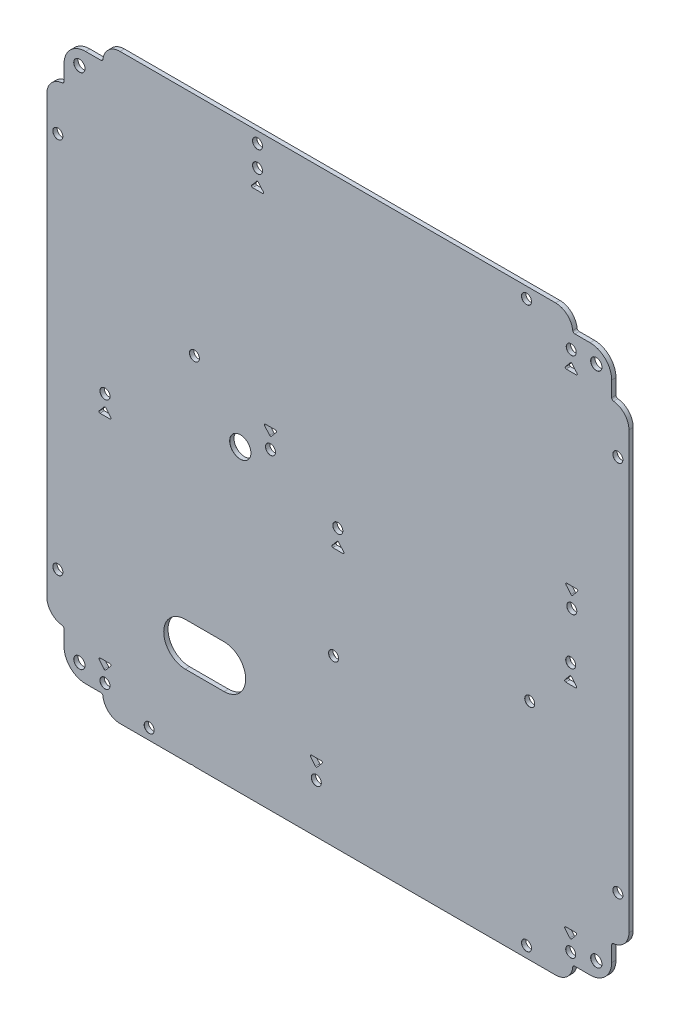
SolidWorks part; units mm, degrees
ref_plane "Front Plane" through (0, 0, 0) normal (0, 0, 1) x (1, 0, 0)
ref_plane "Top Plane" through (0, 0, 0) normal (0, 1, 0) x (1, 0, 0)
ref_plane "Right Plane" through (0, 0, 0) normal (1, 0, 0) x (0, 0, -1)
sketch "Sketch1" plane through (0, 0, 0) normal (0, 0, 1) x (1, 0, 0)
  line L1 (-135, -135) -> (135, -135)
  line L2 (-135, -135) -> (-135, 135)
  line L3 (-135, 135) -> (135, 135)
  line L4 (135, -135) -> (135, 135)
  line L5 (-135, -135) -> (135, 135) construction
  line L6 (-135, 135) -> (135, -135) construction
  point P0 (0, 0)
  dimension "D1" = 270
extrude "Boss-Extrude1" add sketch "Sketch1" along normal mid plane 2
sketch "Sketch5" plane through (0, 0, 0) normal (0, 0, 1) x (1, 0, 0)
  line L1 (-119.875, -119.875) -> (119.875, -119.875) construction
  line L2 (-119.875, -119.875) -> (-119.875, 119.875) construction
  line L3 (-119.875, 119.875) -> (119.875, 119.875) construction
  line L4 (119.875, -119.875) -> (119.875, 119.875) construction
  line L5 (-119.875, -119.875) -> (119.875, 119.875) construction
  line L6 (-119.875, 119.875) -> (119.875, -119.875) construction
  point P0 (0, 0)
  dimension "D1" = 239.75
hole_wizard "Ø5.2 (5.2) Diameter Hole1" positions "Sketch9" profile "Sketch11" hole size "Ø5.2" standard "ANSI Metric" end condition through all
sketch "Sketch9" plane through (0, 0, 1) normal (0, 0, 1) x (1, 0, 0)
  point P0 (119.875, 119.875)
  point P3 (119.875, -119.875)
  point P6 (-119.875, -119.875)
  point P9 (-119.875, 119.875)
sketch "Sketch11" plane through (119.875, 119.875, 1) normal (1, 0, 0) x (0, -1, 0)
  line L0 (0, 0) -> (0, 2)
  line L1 (0, 2) -> (2.625, 2)
  line L2 (2.6, 1.975) -> (2.6, 0.025)
  line L3 (2.6, 0.025) -> (2.625, 0)
  line L5 (2.625, 0) -> (0, 0)
  line L6 (-2.6, 0.025) -> (-2.625, 0) construction
  line L7 (2.625, 2) -> (2.6, 1.975)
  line L8 (-2.625, 2) -> (-2.6, 1.975) construction
  line L11 (0, -6.35) -> (0, 107.95) construction
  dimension "Thru Hole Dia." = 5.2
  dimension "Thru Hole Depth" = 2
  dimension "Near C'Sink Dia." = 5.25
  dimension "Near C'Sink Angle" = 90
  dimension "Far C'Sink Dia." = 5.25
  dimension "Far C'Sink Angle" = 90
sketch "Sketch12" plane through (0, 0, 0) normal (0, 0, 1) x (1, 0, 0)
  line L0 (-127, 109.9443) -> (-127, 117)
  line L1 (-117, 127) -> (-109.9443, 127)
  line L4 (-135, 101) -> (-135, 135)
  line L6 (-135, 135) -> (-101, 135)
  arc A0 (-127, 117) -> (-117, 127) centre (-117, 117) cw
  arc A1 (-108.9505, 127.8889) -> (-101, 135) centre (-101, 127) cw
  arc A2 (-127.8889, 108.9505) -> (-135, 101) centre (-127, 101) ccw
  arc A3 (-109.9443, 127) -> (-108.9505, 127.8889) centre (-109.9443, 128) ccw
  arc A4 (-127, 109.9443) -> (-127.8889, 108.9505) centre (-128, 109.9443) cw
  dimension "D1" = 10
  dimension "D2" = 8
  dimension "D5" = 1
  dimension "D3" = 34
  dimension "D4" = 8
extrude "Cut-Extrude1" cut sketch "Sketch12" against normal through all both and the other way through all
mirror "Mirror1" about plane through (0, 0, 0) normal (1, 0, 0) of "Cut-Extrude1" second plane through (0, 0, 0) second plane normal (0, 1, 0)
sketch "Sketch13" plane through (0, 0, 0) normal (0, 0, 1) x (1, 0, 0)
  line L1 (-129.875, -87.5) -> (129.875, -87.5) construction
  line L2 (-129.875, -87.5) -> (-129.875, 87.5) construction
  line L3 (-129.875, 87.5) -> (129.875, 87.5) construction
  line L4 (129.875, -87.5) -> (129.875, 87.5) construction
  line L5 (-129.875, -87.5) -> (129.875, 87.5) construction
  line L6 (-129.875, 87.5) -> (129.875, -87.5) construction
  point P0 (0, 0)
  dimension "D1" = 259.75
  dimension "D2" = 175
sketch "Sketch16" plane through (0, 0, 0) normal (0, 0, 1) x (1, 0, 0)
  line L0 (-135, 101) -> (-135, -101) construction
  line L1 (-87.5, -129.875) -> (87.5, -129.875) construction
  line L2 (-87.5, -129.875) -> (-87.5, 129.875) construction
  line L3 (-87.5, 129.875) -> (87.5, 129.875) construction
  line L4 (87.5, -129.875) -> (87.5, 129.875) construction
  line L5 (-87.5, -129.875) -> (87.5, 129.875) construction
  line L6 (-87.5, 129.875) -> (87.5, -129.875) construction
  point P0 (0, 0)
  point P6 (-37.25, 129.875)
  dimension "D1" = 175
  dimension "D2" = 259.75
  dimension "D3" = 97.75
hole_wizard "Ø4.6 (4.6) Diameter Hole1" positions "Sketch14" profile "Sketch15" hole size "Ø4.6" standard "ANSI Metric" end condition through all
sketch "Sketch14" plane through (0, 0, 1) normal (0, 0, 1) x (1, 0, 0)
  point P0 (129.875, 87.5)
  point P3 (129.875, -87.5)
  point P6 (-129.875, -87.5)
  point P9 (-129.875, 87.5)
  point P14 (-87.5, -129.875)
  point P17 (87.5, -129.875)
  point P20 (87.5, 129.875)
  point P24 (-37.25, 129.875)
sketch "Sketch15" plane through (129.875, 87.5, 1) normal (1, 0, 0) x (0, -1, 0)
  line L0 (0, 0) -> (0, 2)
  line L1 (0, 2) -> (2.325, 2)
  line L2 (2.3, 1.975) -> (2.3, 0.025)
  line L3 (2.3, 0.025) -> (2.325, 0)
  line L5 (2.325, 0) -> (0, 0)
  line L6 (-2.3, 0.025) -> (-2.325, 0) construction
  line L7 (2.325, 2) -> (2.3, 1.975)
  line L8 (-2.325, 2) -> (-2.3, 1.975) construction
  line L11 (0, -6.35) -> (0, 107.95) construction
  dimension "Thru Hole Dia." = 4.6
  dimension "Thru Hole Depth" = 2
  dimension "Near C'Sink Dia." = 4.65
  dimension "Near C'Sink Angle" = 90
  dimension "Far C'Sink Dia." = 4.65
  dimension "Far C'Sink Angle" = 90
sketch "Sketch17" plane through (0, 0, 0) normal (0, 0, 1) x (1, 0, 0)
  line L0 (-70.75, -88) -> (-52.75, -88) construction
  line L1 (-70.75, -78) -> (-52.75, -78)
  line L2 (-70.75, -98) -> (-52.75, -98)
  line L3 (-101, -135) -> (101, -135) construction
  line L4 (-135, 101) -> (-135, -101) construction
  arc A0 (-70.75, -78) -> (-70.75, -98) centre (-70.75, -88) ccw
  arc A1 (-52.75, -98) -> (-52.75, -78) centre (-52.75, -88) ccw
  point P2 (-61.75, -88)
  dimension "D2" = 38
  dimension "D1" = 20
  dimension "D3" = 37
  dimension "D4" = 54.25
extrude "Cut-Extrude2" cut sketch "Sketch17" along normal through all both and the other way through all
hole_wizard "Ø9.8 (9.8) Diameter Hole1" positions "Sketch18" profile "Sketch19" hole size "Ø9.8" standard "ANSI Metric" end condition through all
sketch "Sketch18" plane through (0, 0, 1) normal (0, 0, 1) x (1, 0, 0)
  line L0 (-135, 101) -> (-135, -101) construction
  line L1 (101, 135) -> (-101, 135) construction
  point P0 (-45.25, 4)
  dimension "D1" = 89.75
  dimension "D2" = 131
sketch "Sketch19" plane through (-45.25, 4, 1) normal (1, 0, 0) x (0, -1, 0)
  line L0 (0, 0) -> (0, 2)
  line L1 (0, 2) -> (4.925, 2)
  line L2 (4.9, 1.975) -> (4.9, 0.025)
  line L3 (4.9, 0.025) -> (4.925, 0)
  line L5 (4.925, 0) -> (0, 0)
  line L6 (-4.9, 0.025) -> (-4.925, 0) construction
  line L7 (4.925, 2) -> (4.9, 1.975)
  line L8 (-4.925, 2) -> (-4.9, 1.975) construction
  line L11 (0, -6.35) -> (0, 107.95) construction
  dimension "Thru Hole Dia." = 9.8
  dimension "Thru Hole Depth" = 2
  dimension "Near C'Sink Dia." = 9.85
  dimension "Near C'Sink Angle" = 90
  dimension "Far C'Sink Dia." = 9.85
  dimension "Far C'Sink Angle" = 90
hole_wizard "Ø4.6 (4.6) Diameter Hole2" positions "Sketch22" profile "Sketch23" hole size "Ø4.6" standard "ANSI Metric" end condition through all
sketch "Sketch22" plane through (0, 0, 1) normal (0, 0, 1) x (1, 0, 0)
  line L0 (-37.25, 129.875) -> (-37.25, 120) construction
  line L2 (101, 135) -> (-101, 135) construction
  line L3 (108.2499, 119.875) -> (119.875, 119.875) construction
  line L4 (-135, 101) -> (-135, -101) construction
  point P0 (-37.25, 120)
  point P9 (108.2499, 119.875)
  point P18 (-31.25, 10)
  point P23 (108.5, 16)
  point P24 (-67.4617, -137.1832)
  dimension "D1" = 15
  dimension "D2" = 243.2499
  dimension "D3" = 125
  dimension "D4" = 103.75
  dimension "D5" = 243.5
  dimension "D6" = 119
sketch "Sketch23" plane through (-37.25, 120, 1) normal (1, 0, 0) x (0, -1, 0)
  line L0 (0, 0) -> (0, 2)
  line L1 (0, 2) -> (2.325, 2)
  line L2 (2.3, 1.975) -> (2.3, 0.025)
  line L3 (2.3, 0.025) -> (2.325, 0)
  line L5 (2.325, 0) -> (0, 0)
  line L6 (-2.3, 0.025) -> (-2.325, 0) construction
  line L7 (2.325, 2) -> (2.3, 1.975)
  line L8 (-2.325, 2) -> (-2.3, 1.975) construction
  line L11 (0, -6.35) -> (0, 107.95) construction
  dimension "Thru Hole Dia." = 4.6
  dimension "Thru Hole Depth" = 2
  dimension "Near C'Sink Dia." = 4.65
  dimension "Near C'Sink Angle" = 90
  dimension "Far C'Sink Dia." = 4.65
  dimension "Far C'Sink Angle" = 90
hole_wizard "Ø4.6 (4.6) Diameter Hole3" positions "Sketch25" profile "Sketch26" hole size "Ø4.6" standard "ANSI Metric" end condition through all
sketch "Sketch25" plane through (0, 0, 1) normal (0, 0, 1) x (1, 0, 0)
  line L0 (-135, 101) -> (-135, -101) construction
  line L1 (-101, -135) -> (-68.2612, -135) construction
  line L3 (108, -6) -> (108, -122.25) construction
  line L5 (-108, -6) -> (-108, -122.25) construction
  point P0 (-108, -6)
  point P2 (0, -6)
  point P4 (108, -6)
  point P6 (-108, -122.25)
  point P8 (-10, -112.25)
  point P10 (108, -122.25)
  dimension "D1" = 27
  dimension "D2" = 135
  dimension "D3" = 243
  dimension "D4" = 129
  dimension "D5" = 12.75
  dimension "D8" = 125
  dimension "D9" = 22.75
sketch "Sketch26" plane through (-108, -6, 1) normal (1, 0, 0) x (0, -1, 0)
  line L0 (0, 0) -> (0, 2)
  line L1 (0, 2) -> (2.325, 2)
  line L2 (2.3, 1.975) -> (2.3, 0.025)
  line L3 (2.3, 0.025) -> (2.325, 0)
  line L5 (2.325, 0) -> (0, 0)
  line L6 (-2.3, 0.025) -> (-2.325, 0) construction
  line L7 (2.325, 2) -> (2.3, 1.975)
  line L8 (-2.325, 2) -> (-2.3, 1.975) construction
  line L11 (0, -6.35) -> (0, 107.95) construction
  dimension "Thru Hole Dia." = 4.6
  dimension "Thru Hole Depth" = 2
  dimension "Near C'Sink Dia." = 4.65
  dimension "Near C'Sink Angle" = 90
  dimension "Far C'Sink Dia." = 4.65
  dimension "Far C'Sink Angle" = 90
sketch "Sketch27" plane through (0, 0, 0) normal (0, 0, 1) x (1, 0, 0)
  line L0 (-39.5489, 111) -> (-34.9511, 111)
  line L1 (-34.5689, 111.8224) -> (-36.8679, 114.5471)
  line L2 (-37.6321, 114.5471) -> (-39.9311, 111.8224)
  line L3 (-37.25, 120) -> (-37.25, 111) construction
  arc A0 (-34.9511, 111) -> (-34.5689, 111.8224) centre (-34.9511, 111.5) ccw
  arc A1 (-39.5489, 111) -> (-39.9311, 111.8224) centre (-39.5489, 111.5) cw
  arc A2 (-36.8679, 114.5471) -> (-37.6321, 114.5471) centre (-37.25, 114.2247) ccw
  point P4 (-37.25, 111)
  point P7 (-33.875, 111)
  point P10 (-40.625, 111)
  point P13 (-37.25, 115)
  dimension "D3" = 0.5
  dimension "D1" = 6.75
  dimension "D2" = 4
  dimension "D4" = 9
extrude "Cut-Extrude3" cut sketch "Sketch27" along normal through all both and the other way through all
sketch "Sketch28" plane through (0, 0, 0) normal (0, 0, 1) x (1, 0, 0)
  point P0 (-37.25, 120)
  point P1 (108.2499, 119.875)
  point P3 (108, -6)
  point P5 (0, -6)
  point P7 (-108, -6)
pattern_sketch "Sketch-Pattern1" of "Cut-Extrude3" driven by "Sketch28"
sketch "Sketch29" plane through (0, 0, 0) normal (0, 0, 1) x (1, 0, 0)
  line L0 (-31.25, 10) -> (-31.25, 19) construction
  line L1 (-33.5489, 19) -> (-28.9511, 19)
  line L2 (-28.5689, 18.1776) -> (-30.8679, 15.4529)
  line L3 (-31.6321, 15.4529) -> (-33.9311, 18.1776)
  line L4 (-37.25, 120) -> (-37.25, 111) construction
  line L5 (-39.5489, 111) -> (-34.9511, 111) construction
  line L6 (-37.6321, 114.5471) -> (-39.9311, 111.8224) construction
  arc A0 (-28.9511, 19) -> (-28.5689, 18.1776) centre (-28.9511, 18.5) cw
  arc A1 (-30.8679, 15.4529) -> (-31.6321, 15.4529) centre (-31.25, 15.7753) cw
  arc A2 (-33.5489, 19) -> (-33.9311, 18.1776) centre (-33.5489, 18.5) ccw
  arc A3 (-34.9511, 111) -> (-34.5689, 111.8224) centre (-34.9511, 111.5) ccw construction
  point P6 (-31.25, 19)
  point P18 (-31.25, 15)
extrude "Cut-Extrude4" cut sketch "Sketch29" against normal through all both and the other way through all
sketch "Sketch30" plane through (0, 0, 0) normal (0, 0, 1) x (1, 0, 0)
  point P0 (-31.25, 10)
  point P1 (108.5, 16)
  point P3 (108, -122.25)
  point P5 (-10, -112.25)
  point P7 (-108, -122.25)
pattern_sketch "Sketch-Pattern2" of "Cut-Extrude4" driven by "Sketch30"
hole_wizard "Ø4.6 (4.6) Diameter Hole4" positions "Sketch31" profile "Sketch32" hole size "Ø4.6" standard "ANSI Metric" end condition through all
sketch "Sketch31" plane through (0, 0, 1) normal (0, 0, 1) x (1, 0, 0)
  line L0 (-135, 101) -> (-135, -101) construction
  line L1 (101, 135) -> (-101, 135) construction
  point P0 (-66.5, 30)
  point P2 (-2, -58.25)
  point P4 (89, -31)
  dimension "D1" = 68.5
  dimension "D2" = 105
  dimension "D3" = 133
  dimension "D4" = 224
  dimension "D5" = 193.25
  dimension "D6" = 166
sketch "Sketch32" plane through (-66.5, 30, 1) normal (1, 0, 0) x (0, -1, 0)
  line L0 (0, 0) -> (0, 2)
  line L1 (0, 2) -> (2.325, 2)
  line L2 (2.3, 1.975) -> (2.3, 0.025)
  line L3 (2.3, 0.025) -> (2.325, 0)
  line L5 (2.325, 0) -> (0, 0)
  line L6 (-2.3, 0.025) -> (-2.325, 0) construction
  line L7 (2.325, 2) -> (2.3, 1.975)
  line L8 (-2.325, 2) -> (-2.3, 1.975) construction
  line L11 (0, -6.35) -> (0, 107.95) construction
  dimension "Thru Hole Dia." = 4.6
  dimension "Thru Hole Depth" = 2
  dimension "Near C'Sink Dia." = 4.65
  dimension "Near C'Sink Angle" = 90
  dimension "Far C'Sink Dia." = 4.65
  dimension "Far C'Sink Angle" = 90
sketch "Sketch33" plane through (0, 0, 0) normal (0, 0, 1) x (1, 0, 0)
  line L0 (-66.6621, -135) -> (101, -135) construction
  line L1 (-111.75, -125) -> (111.75, -125)
  line L2 (-111.75, -125) -> (-111.75, -1.5)
  line L3 (-111.75, -1.5) -> (111.75, -1.5)
  line L4 (111.75, -125) -> (111.75, -1.5)
  line L5 (-101, -135) -> (-68.2612, -135) construction
  line L6 (-110.5, -12) -> (-98, -12)
  line L7 (-110.5, -12) -> (-110.5, -81.5)
  line L8 (-110.5, -81.5) -> (-98, -81.5)
  line L9 (-98, -12) -> (-98, -81.5)
  line L10 (-95.5, -12) -> (-83, -12)
  line L11 (-95.5, -12) -> (-95.5, -81.5)
  line L12 (-95.5, -81.5) -> (-83, -81.5)
  line L13 (-83, -12) -> (-83, -81.5)
  line L14 (-135, 101) -> (-135, -101) construction
  line L16 (-26.25, -14) -> (-25.25, -14)
  line L17 (-26.25, -14) -> (-26.25, -20.5)
  line L18 (-26.25, -20.5) -> (-25.25, -20.5)
  line L19 (-25.25, -14) -> (-25.25, -20.5)
  line L20 (-13.5, -14) -> (-12.5, -14)
  line L21 (-13.5, -14) -> (-13.5, -20.5)
  line L22 (-13.5, -20.5) -> (-12.5, -20.5)
  line L23 (-12.5, -14) -> (-12.5, -20.5)
  point P0 (0, -1.5)
  point P29 (-12.5, -17.25)
  dimension "D1" = 10
  dimension "D2" = 123.5
  dimension "D3" = 223.5
  dimension "D4" = 12.5
  dimension "D5" = 27.5
  dimension "D6" = 69.5
  dimension "D7" = 123
  dimension "D8" = 52
  dimension "D9" = 1
  dimension "D10" = 6.5
  dimension "D11" = 122.5
  dimension "D12" = 111
  dimension "D13" = 13.75
sketch "Sketch35" plane through (0, 0, 0) normal (0, 0, 1) x (1, 0, 0)
  circle A0 centre (-70.75, -88) radius 7.5
  circle A1 centre (-52.75, -88) radius 7.5
  dimension "D1" = 15
sketch "Sketch34" plane through (0, 0, 0) normal (0, 0, 1) x (1, 0, 0)
  line L0 (-32.125, -12.5) -> (-19.375, -12.5)
  line L1 (-19.375, -12.5) -> (-6.625, -12.5)
  line L2 (-26.25, -14) -> (-25.25, -14) construction
  line L3 (-13.5, -14) -> (-12.5, -14) construction
  line L4 (-44.1682, -104.5679) -> (-79.3318, -104.5679)
  line L7 (-70.75, -98) -> (-52.75, -98) construction
  text T0 "+12V"
  text T1 "GND"
  text T2 "+12v     GND"
  point P4 (-25.75, -12.5)
  point P7 (-25.75, -14)
  point P8 (-13, -12.5)
  point P11 (-13, -14)
  point P13 (-79.015, -104.5679)
  point P17 (-61.75, -104.5679)
  point P18 (0, 0)
  point P21 (-61.75, -98)
  dimension "D1" = 1.5
sketch "Sketch36" plane through (0, 0, 0) normal (0, 0, 1) x (1, 0, 0)
  line L1 (-104.25, -12) -> (-104.25, -81.5)
  line L2 (-110.5, -12) -> (-98, -12) construction
  line L3 (-110.5, -81.5) -> (-98, -81.5) construction
  line L4 (-89.25, -12) -> (-89.25, -81.5)
  line L5 (-95.5, -12) -> (-83, -12) construction
  line L6 (-95.5, -81.5) -> (-83, -81.5) construction
  text T0 "to Spraybox"
  text T1 "to fluid junction box"
